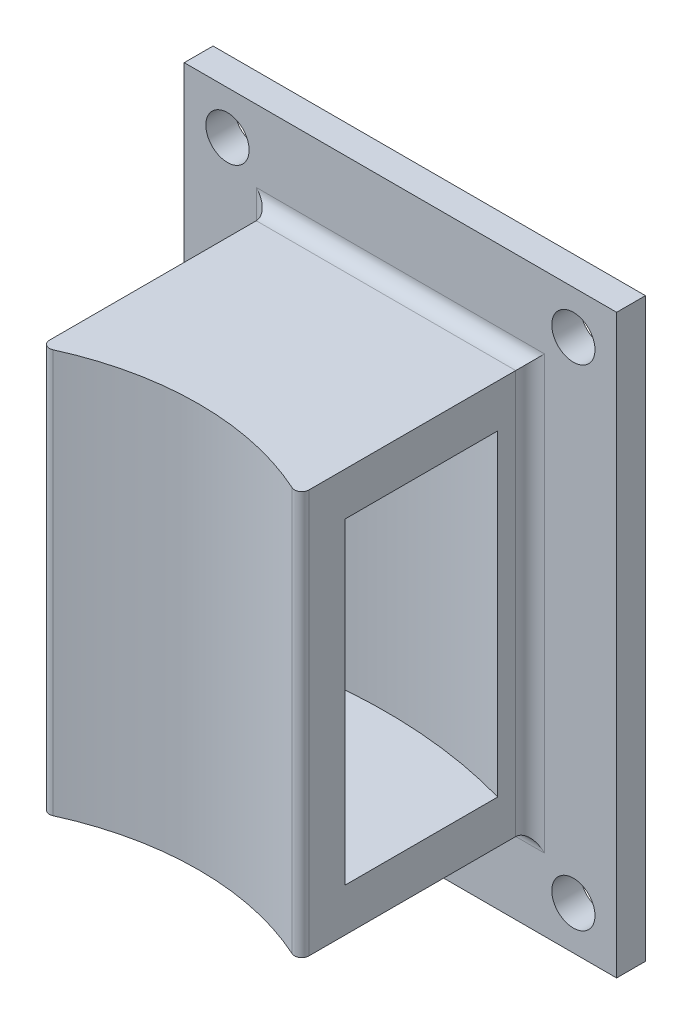
SolidWorks part; units mm, degrees
ref_plane "前视基准面" through (0, 0, 0) normal (0, 0, 1) x (1, 0, 0)
ref_plane "上视基准面" through (0, 0, 0) normal (0, 1, 0) x (1, 0, 0)
ref_plane "右视基准面" through (0, 0, 0) normal (1, 0, 0) x (0, 0, -1)
sketch "草图1" plane through (0, 0, 0) normal (0, 1, 0) x (1, 0, 0)
  line L0 (-9, 36) -> (-9, 31.749)
  line L1 (0, -1000) -> (0, 49000) construction
  line L2 (9, 36) -> (9, 31.749)
  line L3 (-9, 36) -> (9, 36)
  line L4 (-9, 21.166) -> (-9, 17.8606)
  line L5 (9, 21.166) -> (9, 17.8606)
  arc A0 (9, 17.8606) -> (-9, 17.8606) centre (0, 0) ccw
  arc A1 (9, 21.166) -> (-9, 21.166) centre (0, 0) ccw
  arc A2 (9, 31.749) -> (-9, 31.749) centre (0, 0) ccw
  circle A3 centre (0, 0) radius 33 construction
  circle A4 centre (0, 0) radius 23 construction
  circle A5 centre (0, 0) radius 20 construction
  dimension "D1" = 40
  dimension "D4" = 18
  dimension "D5" = 36
  dimension "D2" = 3
  dimension "D3" = 10
extrude "凸台-拉伸1" add sketch "草图1" along normal mid plane 22
sketch "草图2" plane through (0, 11, 0) normal (0, 1, 0) x (1, 0, 0)
  line L0 (-9, 36) -> (-9, 17.8606)
  line L2 (9, 17.8606) -> (9, 21.166)
  line L3 (9, 36) -> (-9, 36)
  line L4 (-9, 36) -> (-9, 31.749)
  line L5 (9, 31.749) -> (9, 36)
  line L6 (9, 36) -> (-9, 36)
  line L9 (-9, 21.166) -> (-9, 17.8606)
  line L12 (9, 17.8606) -> (9, 36)
  arc A1 (9, 31.749) -> (-9, 31.749) centre (0, 0) ccw
  arc A4 (9, 17.8606) -> (-9, 17.8606) centre (0, 0) ccw
  arc A5 (9, 21.166) -> (-9, 21.166) centre (0, 0) ccw
  arc A6 (9, 17.8606) -> (-9, 17.8606) centre (0, 0) ccw
  dimension "D1" = 0
  dimension "D2" = 0
extrude "凸台-拉伸2" add sketch "草图2" along normal blind 3
mirror "镜向1" about plane through (0, 0, 0) normal (0, 1, 0) of "凸台-拉伸2"
sketch "草图5" plane through (0, 0, -36) normal (0, 0, -1) x (-1, 0, 0)
  line L8 (-9, 14) -> (-9, -14)
  line L9 (-9, -14) -> (9, -14)
  line L10 (9, -14) -> (9, 14)
  line L11 (9, 14) -> (-9, 14)
  line L12 (-9, 14) -> (-9, -14)
  line L13 (-9, -14) -> (9, -14)
  line L14 (9, -14) -> (9, 14)
  line L15 (9, 14) -> (-9, 14)
  line L20 (-15, 20) -> (-15, -20)
  line L21 (-15, -20) -> (15, -20)
  line L22 (15, -20) -> (15, 20)
  line L23 (15, 20) -> (-15, 20)
  line L24 (-15, 20) -> (-15, -20)
  line L25 (-15, -20) -> (15, -20)
  line L26 (15, -20) -> (15, 20)
  line L27 (15, 20) -> (-15, 20)
  dimension "D1" = 0
  dimension "D2" = 6
extrude "凸台-拉伸3" add sketch "草图5" against normal blind 2
sketch "草图6" plane through (0, 0, -34) normal (0, 0, 1) x (1, 0, 0)
  line L0 (15, 20) -> (15, -20) construction
  line L1 (-15, 20) -> (15, 20) construction
  line L2 (0, 20) -> (0, -20) construction
  line L3 (15, -20) -> (-15, -20) construction
  line L4 (-15, 0) -> (15, 0) construction
  line L5 (-15, -20) -> (-15, 20) construction
  circle A0 centre (12, 17) radius 1.5
  circle A1 centre (-12, 17) radius 1.5
  circle A2 centre (12, -17) radius 1.5
  circle A3 centre (-12, -17) radius 1.5
  dimension "D1" = 3
  dimension "D2" = 24
  dimension "D3" = 34
extrude "切除-拉伸1" cut sketch "草图6" against normal through all
fillet "圆角1" radius 1 4 edges at (9, 0, -34) (0, 14, -34) (-9, 0, -34) (0, -14, -34)
fillet "圆角2" radius 0.5 2 edges at (9, 0, -17.8606) (-9, 0, -17.8606)
